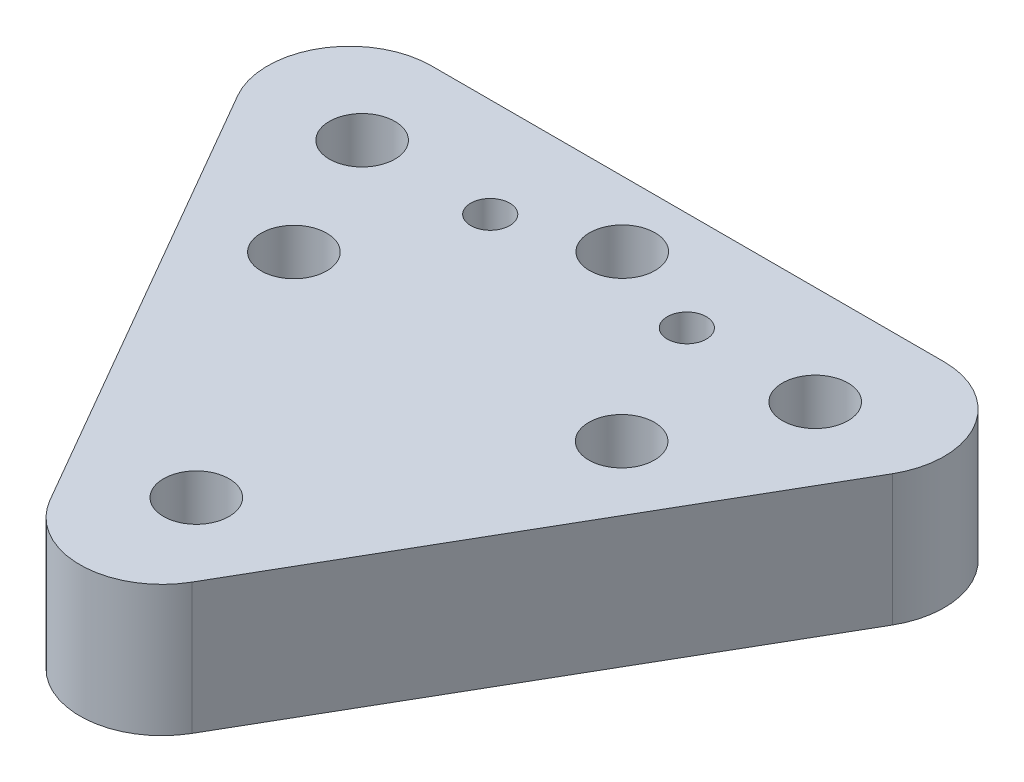
SolidWorks part; units mm, degrees
material "Chrome Stainless Steel"
ref_plane "Front Plane" through (0, 0, 0) normal (0, 0, 1) x (1, 0, 0)
ref_plane "Top Plane" through (0, 0, 0) normal (0, 1, 0) x (1, 0, 0)
ref_plane "Right Plane" through (0, 0, 0) normal (1, 0, 0) x (0, 0, -1)
sketch "Sketch1" plane through (0, 0, 0) normal (0, 1, 0) x (1, 0, 0)
  line L0 (-5.186, 3.3162) -> (2.6377, -10.235)
  line L1 (6.9679, -10.235) -> (14.7916, 3.3162)
  line L2 (12.6266, 7.0662) -> (-3.021, 7.0662)
  line L3 (-1.2742, -3.4594) -> (15.2246, 6.0662) construction
  line L4 (4.8028, 7.0662) -> (4.8028, -11.985) construction
  line L5 (10.8797, -3.4594) -> (-5.6191, 6.0662) construction
  circle A0 centre (-2.1106, 4.0406) radius 2.3812
  circle A1 centre (-2.1106, 4.0406) radius 1
  circle A2 centre (11.7162, 4.0406) radius 1
  circle A3 centre (4.8028, -7.9338) radius 1
  circle A4 centre (4.8028, -7.9338) radius 2.3812
  circle A5 centre (11.7162, 4.0406) radius 2.3812
  arc A15 (-5.186, 3.3162) -> (-3.021, 7.0662) centre (-3.021, 4.5662) cw
  arc A16 (14.7916, 3.3162) -> (12.6266, 7.0662) centre (12.6266, 4.5662) ccw
  arc A17 (6.9679, -10.235) -> (2.6377, -10.235) centre (4.8028, -8.985) cw
  point P9 (-7.3511, 7.0662)
  point P12 (4.8028, -13.985)
  point P22 (4.8028, 0.0491)
  dimension "D1" = 4.7625
  dimension "D5" = 2
  dimension "D9" = 4.7625
  dimension "D10" = 4.7625
  dimension "D12" = 2.5
  dimension "D2" = 300
  dimension "D3" = 60
  dimension "D4" = 24.3078
  dimension "D6" = 15
  dimension "D7" = 15
  dimension "D8" = 15
extrude "Extrude1" add sketch "Sketch1" along normal blind 4 contours A0 | A17 L1 A16 L2 A15 L0 A5 A4 A0 | A5 | A4 region at (4.8028, 0, -0.0491) region at (-4.4245, 0, -4.0406) region at (2.4889, 0, 7.9338) region at (9.4023, 0, -4.0406)
extrude "Extrude4" cut sketch "Sketch1<3>" along normal blind 2 contours A4 | A5 | A0 region at (2.4889, 0, 7.9338) region at (9.4023, 0, -4.0406)
sketch "Sketch1<3>" plane through (0, 0, 0) normal (0, 1, 0) x (1, 0, 0) same geometry as "Sketch1"
sketch "Sketch2" plane through (0, 0, 0) normal (0, -1, 0) x (1, 0, 0)
  line L0 (4.8028, -8.1773) -> (4.8028, 12.2506) construction
  line L1 (-3.5817, 4.7917) -> (16.7524, -6.9482) construction
  line L2 (12.7038, 4.5125) -> (-7.1468, -6.9482) construction
hole_wizard "M2x0.4 Tapped Hole1" positions "3DSketch1" profile "Sketch3" tap size "M2x0.4" standard "Ansi Metric"
sketch3d "3DSketch1"
  line L0 (4.8028, 0, -8.1773) -> (4.8028, 0, 12.2506) construction
  line L1 (12.7038, 0, 4.5125) -> (-7.1468, 0, -6.9482) construction
  point P0 (4.8028, 0, -0.0491)
sketch "Sketch3" plane through (4.8028, 0, -0.0491) normal (1, 0, 0) x (0, 0, -1)
  line L0 (0, 0) -> (0, 3.4807)
  line L1 (0, 3.4807) -> (0.8, 3)
  line L2 (0.8, 3) -> (0.8, 0)
  line L5 (0.8, 0) -> (0, 0)
  line L10 (0, 3.4807) -> (-0.8, 3) construction
  line L11 (0, -6.35) -> (0, 107.95) construction
  dimension "Tap Drill Dia." = 1.6
  dimension "Tap Drill Depth" = 3
  dimension "Drill Angle" = 118
hole_wizard "Ø2.0 (2) Diameter Hole1" positions "3DSketch2" profile "Sketch4" hole size "Ø2.0" standard "Ansi Metric"
sketch3d "3DSketch2"
  line L2 (4.8028, 0, -8.1773) -> (4.8028, 0, 12.2506) construction
  line L5 (12.6266, 0, -7.0662) -> (-3.021, 0, -7.0662) construction
  point P8 (4.8028, 0, -5.0662)
  point P24 (9.8028, 0, -0.0462)
  point P26 (-0.1972, 0, -0.0462)
  dimension "D1" = 7.02
  dimension "D4" = 7.02
  dimension "D2" = 5
  dimension "D3" = 2
  dimension "D5" = 5
sketch "Sketch4" plane through (4.8028, 0, -5.0662) normal (1, 0, 0) x (0, 0, -1)
  line L0 (0, 0) -> (0, 10.6009)
  line L1 (0, 10.6009) -> (1, 10)
  line L2 (1, 10) -> (1, 0)
  line L5 (1, 0) -> (0, 0)
  line L10 (0, 10.6009) -> (-1, 10) construction
  line L11 (0, -6.35) -> (0, 107.95) construction
  dimension "Hole Dia." = 2
  dimension "Hole Depth" = 10
  dimension "Drill Angle" = 118
sketch "Sketch6" plane through (0, 4, 0) normal (0, 1, 0) x (-1, 0, 0)
  line L0 (-4.8028, -8.9331) -> (-4.8028, 13.1713) construction
hole_wizard "#0-80 Tapped Hole2" positions "3DSketch4" profile "Sketch7" tap size "#0-80" standard "Ansi Inch" end condition up to next
sketch3d "3DSketch4"
  line L0 (4.8028, 4, -8.9331) -> (4.8028, 4, 13.1713) construction
  line L1 (12.6266, 4, -7.0662) -> (-3.021, 4, -7.0662) construction
  point P0 (1.8028, 4, -4.0362)
  point P2 (7.8028, 4, -4.0362)
  dimension "D1" = 3
  dimension "D2" = 3
  dimension "D3" = 3.03
  dimension "D4" = 3.03
sketch "Sketch7" plane through (1.8028, 4, -4.0362) normal (1, 0, 0) x (0, 0, 1)
  line L0 (0, 0) -> (0, 4)
  line L1 (0, 4) -> (0.5956, 4)
  line L2 (0.5956, 4) -> (0.5956, 0)
  line L5 (0.5956, 0) -> (0, 0)
  line L11 (0, -6.35) -> (0, 107.95) construction
  dimension "Thread Major Dia." = 1.1913
  dimension "Thru Tap Drill Depth" = 4
